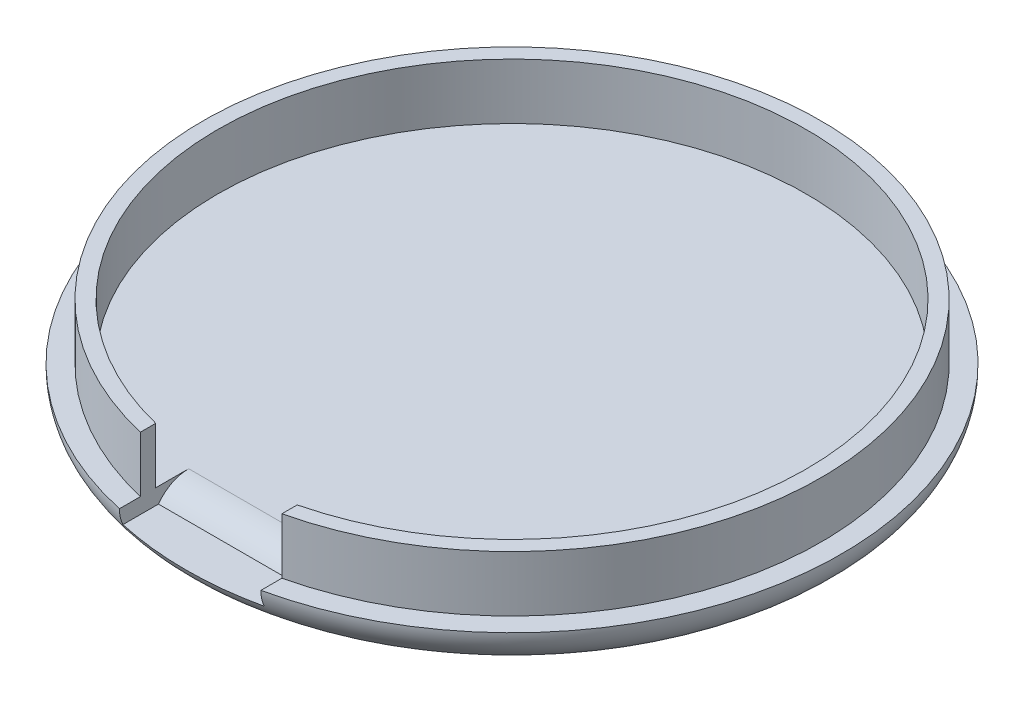
SolidWorks part; units mm, degrees
ref_plane "Front Plane" through (0, 0, 0) normal (0, 0, 1) x (1, 0, 0)
ref_plane "Top Plane" through (0, 0, 0) normal (0, 1, 0) x (1, 0, 0)
ref_plane "Right Plane" through (0, 0, 0) normal (1, 0, 0) x (0, 0, -1)
sketch "Sketch1" plane through (0, 0, 0) normal (0, 1, 0) x (1, 0, 0)
  circle A0 centre (0, 0) radius 17.71
  circle A1 centre (0, 0) radius 16.61
  circle A2 centre (0, 0) radius 16.71
  circle A3 centre (0, 0) radius 15.81
  dimension "D1" = 35.42
  dimension "D2" = 33.22
  dimension "D3" = 0.1
  dimension "D4" = 0.8
extrude "Boss-Extrude1" add sketch "Sketch1" along normal blind 2 contours A0
extrude "Boss-Extrude2" add sketch "Sketch1<3>" along normal blind 5 contours A1 A3 region at (-16.1402, 0, 0)
sketch "Sketch1<3>" plane through (0, 0, 0) normal (0, 1, 0) x (1, 0, 0) same geometry as "Sketch1"
fillet "Fillet1" radius 2 1 edges at (0, 0, 17.71)
ref_plane "Plane1" through (0, 0, 20) normal (0, 0, 1) x (1, 0, 0)
sketch "Sketch3" plane through (0, 0, 20) normal (0, 0, 1) x (1, 0, 0)
  line L6 (3.7999, 1.1665) -> (-3.7999, 1.1665)
  line L7 (3.7999, 1.1665) -> (3.7999, 8.21)
  line L8 (3.7999, 8.21) -> (-3.7999, 8.21)
  line L9 (-3.7999, 1.1665) -> (-3.7999, 8.21)
  line L10 (3.7999, 1.1665) -> (-3.7999, 8.21) construction
  line L11 (3.7999, 8.21) -> (-3.7999, 1.1665) construction
  point P4 (0, 4.6883)
  point P5 (0, 3.1349)
  point P6 (-4.6829, 8.2612)
  point P7 (0, 4.8588)
  point P8 (0, 4.6883)
extrude "Cut-Extrude1" cut sketch "Sketch3" against normal blind 4.8
fillet "Fillet2" radius 2 1 edges at (0, 2, 15.2)
